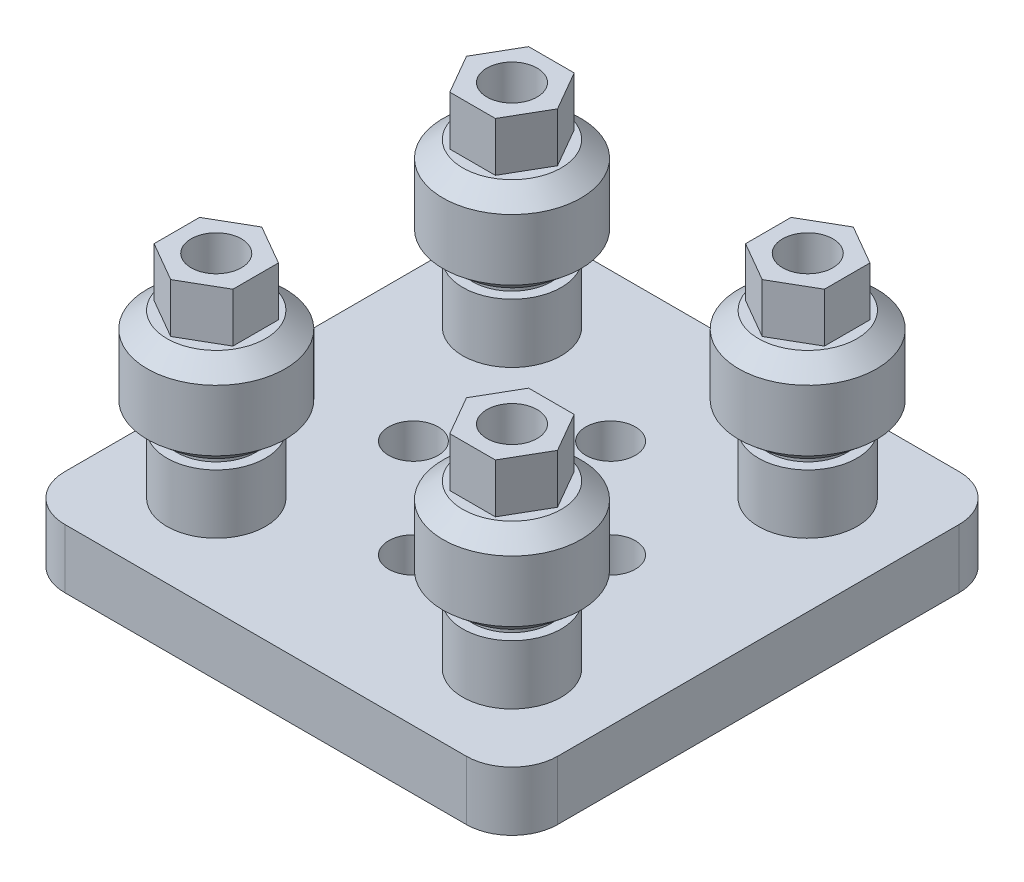
SolidWorks part; units mm, degrees
ref_plane "Спереди" through (0, 0, 0) normal (0, 0, 1) x (1, 0, 0)
ref_plane "Сверху" through (0, 0, 0) normal (0, 1, 0) x (1, 0, 0)
ref_plane "Справа" through (0, 0, 0) normal (1, 0, 0) x (0, 0, -1)
other "Configuration Table"
sketch "Эскиз1" plane through (0, 0, 0) normal (0, 1, 0) x (1, 0, 0)
  line L0 (0, 10) -> (0, 0) construction
  line L1 (-25, -25) -> (25, -25) construction
  line L2 (-25, -25) -> (-25, 20.36) construction
  line L3 (-20.36, 25) -> (25, 25) construction
  line L4 (25, -25) -> (25, 25) construction
  line L5 (-25, -25) -> (25, 25) construction
  line L6 (-25, 25) -> (25, -25) construction
  line L7 (10, 0) -> (0, 0) construction
  line L8 (0, -10) -> (0, 0) construction
  line L9 (-10, 0) -> (0, 0) construction
  line L10 (-23.641, 23.641) -> (0, 0) construction
  line L11 (25, 25) -> (-25, -25) construction
  line L12 (25, -25) -> (-25, 25) construction
  line L13 (-25, -25) -> (25, 25) construction
  line L14 (20.36, -25) -> (-20.36, -25)
  line L15 (25, -20.36) -> (25, 20.36)
  line L16 (-20.36, 25) -> (20.36, 25)
  line L17 (-25, 20.36) -> (-25, -20.36)
  circle A0 centre (-15, 15) radius 3.6
  circle A1 centre (15, 15) radius 3.6
  circle A2 centre (15, -15) radius 2.55
  circle A3 centre (-15, -15) radius 2.55
  circle A4 centre (0, 0) radius 2.51
  circle A5 centre (0, 10) radius 2.51
  circle A6 centre (10, 0) radius 2.51
  circle A7 centre (0, -10) radius 2.51
  circle A8 centre (-10, 0) radius 2.51
  arc A9 (-20.36, 25) -> (-25, 20.36) centre (-20.36, 20.36) ccw
  arc A10 (25, 20.36) -> (20.36, 25) centre (20.36, 20.36) ccw
  arc A11 (20.36, -25) -> (25, -20.36) centre (20.36, -20.36) ccw
  arc A12 (-25, -20.36) -> (-20.36, -25) centre (-20.36, -20.36) ccw
  point P0 (0, 0)
  point P19 (-23.641, 23.641)
  point P27 (0, 0)
  point P48 (0, 0)
  dimension "D4" = 7.2
  dimension "D5" = 7.2
  dimension "D6" = 5.1
  dimension "D7" = 5.1
  dimension "D8" = 5.02
  dimension "D9" = 5.02
  dimension "D12" = 9.28
  dimension "D1" = 50
  dimension "D2" = 50
  dimension "D3" = 30
  dimension "D10" = 10
  dimension "D11" = 4
  dimension "D13" = 4
extrude "Бобышка-Вытянуть1" add sketch "Эскиз1" along normal blind 6
sketch "Эскиз2" plane through (0, 0, 0) normal (0, 1, 0) x (1, 0, 0)
  circle A8 centre (-15, 15) radius 6
  circle A9 centre (-15, 15) radius 6
  circle A11 centre (15, 15) radius 6
  circle A12 centre (15, 15) radius 6
  circle A14 centre (-15, -15) radius 5.05
  circle A15 centre (-15, -15) radius 5.05
  circle A17 centre (15, -15) radius 5.05
  circle A18 centre (15, -15) radius 5.05
  dimension "D1" = 2.4
  dimension "D2" = 2.4
  dimension "D3" = 2.5
  dimension "D4" = 2.5
extrude "Вырез-Вытянуть1" cut sketch "Эскиз2" along normal blind 2
sketch "Эскиз3" plane through (0, 6, 0) normal (0, 1, 0) x (1, 0, 0)
  line L0 (-23.641, 23.641) -> (23.641, -23.641) construction
  line L1 (-15, 20) -> (-15, 10) construction
  arc A0 (-20.36, 25) -> (-25, 20.36) centre (-20.36, 20.36) ccw construction
  arc A1 (20.36, -25) -> (25, -20.36) centre (20.36, -20.36) ccw construction
  circle A4 centre (-15, 15) radius 5
  circle A5 centre (-15, 15) radius 2.55
  dimension "D1" = 10
  dimension "D2" = 5.1
extrude "втулка" add sketch "Эскиз3" along normal blind 6 separate body
sketch "Эскиз4" plane through (0, 12, 0) normal (0, 1, 0) x (1, 0, 0)
  line L0 (-15, 19) -> (-15, 11) construction
  circle A0 centre (-15, 15) radius 2.55
  circle A1 centre (-15, 15) radius 4
  dimension "D1" = 8
  dimension "D2" = 5.1
extrude "шайба" add sketch "Эскиз4" along normal blind 1
sketch3d "Трехмерный эскиз2"
  line L0 (-15, 12, -19) -> (-15, 12, -11) construction
sketch "Эскиз5" plane through (-15, 0, 0) normal (1, 0, 0) x (0, 0, -1)
  line L0 (11, 13) -> (19, 13) construction
  line L1 (19, 13) -> (11, 13) construction
  line L2 (15, 13) -> (15, 19.7752) construction
  line L3 (17.55, 13) -> (17.55, 22.5)
  line L4 (17.55, 22.5) -> (20, 22.5)
  line L5 (20, 22.5) -> (22, 20.85)
  line L6 (22, 20.85) -> (22, 14.65)
  line L7 (22, 14.65) -> (20, 13)
  line L8 (20, 13) -> (17.55, 13)
  point P8 (15, 13)
  point P11 (22, 17.75)
  point P16 (17.55, 17.75)
  dimension "D1" = 2.55
  dimension "D2" = 2
  dimension "D3" = 5
  dimension "D4" = 6.2
  dimension "D6" = 9.5
revolve "ролик" add sketch "Эскиз5" angle 360 about L2
sketch "Эскиз6" plane through (0, 22.5, 0) normal (0, 1, 0) x (1, 0, 0)
  line L0 (-17.3094, 11) -> (-19.6188, 15)
  line L1 (-19.6188, 15) -> (-17.3094, 19)
  line L2 (-17.3094, 19) -> (-12.6906, 19)
  line L3 (-12.6906, 19) -> (-10.3812, 15)
  line L4 (-10.3812, 15) -> (-12.6906, 11)
  line L5 (-12.6906, 11) -> (-17.3094, 11)
  circle A0 centre (-15, 15) radius 4 construction
  circle A2 centre (-15, 15) radius 2.55
  dimension "D1" = 8
  dimension "D2" = 5.1
extrude "гайка" add sketch "Эскиз6" along normal blind 5
pattern_circular "Круговой массив10" count 4 over 360 about axis through (0, 6, 0) along (0, -1, 0) of bodies 108
